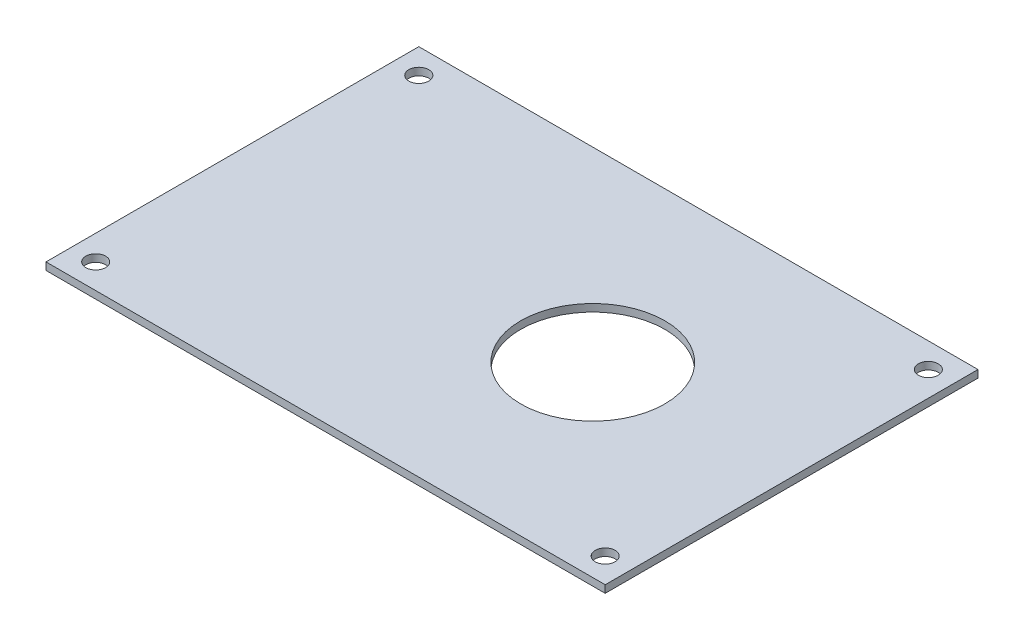
SolidWorks part; units mm, degrees
ref_plane "Front Plane" through (0, 0, 0) normal (0, 0, 1) x (1, 0, 0)
ref_plane "Top Plane" through (0, 0, 0) normal (0, 1, 0) x (1, 0, 0)
ref_plane "Right Plane" through (0, 0, 0) normal (1, 0, 0) x (0, 0, -1)
sketch "Sketch1" plane through (0, 0, 0) normal (0, 1, 0) x (1, 0, 0)
  line L1 (-112.5, -75) -> (112.5, -75)
  line L2 (-112.5, -75) -> (-112.5, 75)
  line L3 (-112.5, 75) -> (112.5, 75)
  line L4 (112.5, -75) -> (112.5, 75)
  line L5 (-112.5, -75) -> (112.5, 75) construction
  line L6 (-112.5, 75) -> (112.5, -75) construction
  point P0 (0, 0)
  dimension "D1" = 225
  dimension "D2" = 150
extrude "Boss-Extrude1" add sketch "Sketch1" along normal blind 3
sketch "Sketch2" plane through (0, 3, 0) normal (0, 1, 0) x (1, 0, 0)
  line L0 (-112.5, -75) -> (112.5, -75) construction
  line L1 (-112.5, 75) -> (-112.5, -75) construction
  line L2 (-112.5, 0) -> (112.5, 0) construction
  line L3 (112.5, -75) -> (112.5, 75) construction
  line L4 (0, -75) -> (0, 75) construction
  line L5 (112.5, 75) -> (-112.5, 75) construction
  circle A0 centre (-102.5, -65) radius 4
  circle A1 centre (-102.5, 65) radius 4
  circle A2 centre (102.5, -65) radius 4
  circle A3 centre (102.5, 65) radius 4
  point P12 (0, 0)
  point P18 (0, 0)
  dimension "D1" = 8
  dimension "D2" = 10
  dimension "D3" = 10
extrude "Cut-Extrude1" cut sketch "Sketch2" against normal blind 3
sketch "Sketch3" plane through (0, 3, 0) normal (0, 1, 0) x (1, 0, 0)
  line L0 (-112.5, 75) -> (-112.5, -75) construction
  circle A0 centre (32.5, 0) radius 29
  dimension "D1" = 58
  dimension "D2" = 145
extrude "Cut-Extrude2" cut sketch "Sketch3" against normal blind 3
